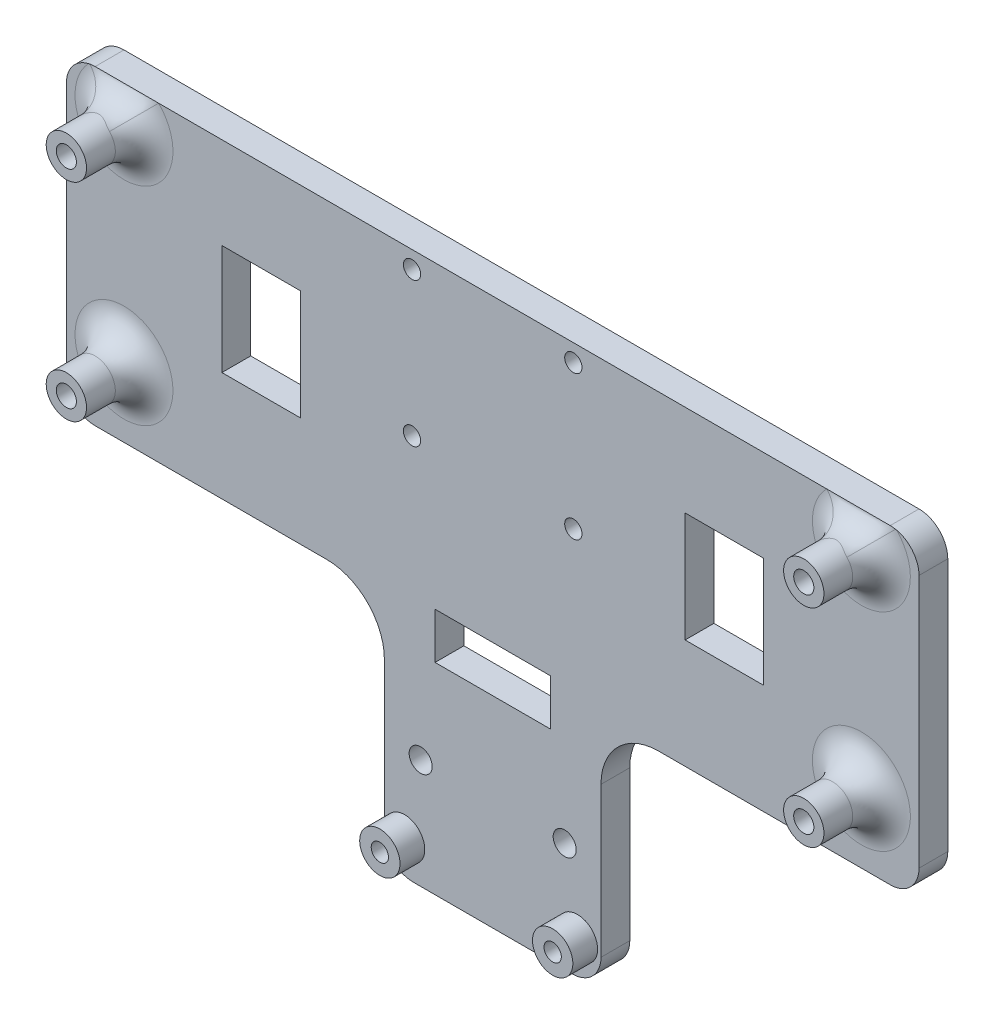
SolidWorks part; units mm, degrees
ref_plane "Front Plane" through (0, 0, 0) normal (0, 0, 1) x (1, 0, 0)
ref_plane "Top Plane" through (0, 0, 0) normal (0, 1, 0) x (1, 0, 0)
ref_plane "Right Plane" through (0, 0, 0) normal (1, 0, 0) x (0, 0, -1)
sketch "Sketch1" plane through (0, 0, 0) normal (0, 1, 0) x (1, 0, 0)
  line L0 (0, 0) -> (0, 178.218) construction
  line L1 (61, 138.218) -> (74, 138.218)
  line L2 (74, 138.218) -> (74, 181.218)
  line L3 (74, 181.218) -> (-74, 181.218)
  line L4 (0, 181.218) -> (0, 178.218)
  line L5 (-71, 178.218) -> (71, 178.218)
  line L6 (71, 178.218) -> (71, 143.218)
  line L7 (71, 143.218) -> (61, 143.218)
  line L8 (61, 143.218) -> (61, 138.218)
  line L9 (-61, 143.218) -> (-61, 138.218)
  line L10 (-71, 143.218) -> (-61, 143.218)
  line L11 (-71, 178.218) -> (-71, 143.218)
  line L12 (-74, 138.218) -> (-74, 181.218)
  line L13 (-61, 138.218) -> (-74, 138.218)
  dimension "D1" = 10
  dimension "D2" = 5
  dimension "D3" = 74
  dimension "D4" = 3
  dimension "D5" = 3
  dimension "D6" = 35
extrude "Boss-Extrude1" add sketch "Sketch1" along normal blind 110 contours L13 L9 L10 L11 L5 L4 L3 L12 | L7 L8 L1 L2 L3 L4 L5 L6
sketch "Sketch2" plane through (74, 0, 0) normal (1, 0, 0) x (0, 0, -1)
  line L0 (138.218, 66.5) -> (165.218, 66.5)
  line L1 (138.218, 110) -> (138.218, 0) construction
  line L2 (165.218, 66.5) -> (165.218, 100.5)
  line L3 (165.218, 100.5) -> (138.218, 100.5)
  line L4 (138.218, 100.5) -> (138.218, 66.5)
  line L5 (138.218, 110) -> (181.218, 110) construction
  dimension "D1" = 34
  dimension "D2" = 9.5
  dimension "D3" = 27
extrude "Cut-Extrude1" cut sketch "Sketch2" against normal blind 171
sketch "Sketch5" plane through (0, 0, -138.218) normal (0, 0, 1) x (1, 0, 0)
  line L0 (-61, 66.5) -> (-71, 66.5)
  line L1 (-74, 66.5) -> (-61, 66.5) construction
  line L2 (-71, 66.5) -> (-71, 54)
  line L3 (-71, 54) -> (-61, 54)
  line L4 (-61, 66.5) -> (-61, 0) construction
  line L5 (-61, 54) -> (-61, 66.5)
  line L6 (0, 0) -> (0, 110) construction
  line L7 (-71, 0) -> (71, 0) construction
  line L8 (-71, 110) -> (71, 110) construction
  line L9 (61, 54) -> (61, 66.5)
  line L10 (71, 54) -> (61, 54)
  line L11 (71, 66.5) -> (71, 54)
  line L12 (61, 66.5) -> (71, 66.5)
  dimension "D1" = 12.5
extrude "Cut-Extrude4" cut sketch "Sketch5" against normal blind 10 contours L5 L0 L2 L3 | L9 L12 L11 L10
sketch "Sketch7" plane through (74, 0, 0) normal (1, 0, 0) x (0, 0, -1)
  line L0 (181.218, 110) -> (138.218, 110)
  line L1 (138.218, 110) -> (138.218, 54)
  line L2 (138.218, 66.5) -> (138.218, 0) construction
  line L3 (138.218, 54) -> (181.218, 54)
  line L4 (181.218, 110) -> (181.218, 0) construction
  line L5 (181.218, 54) -> (181.218, 110)
  dimension "D1" = 56
extrude "Cut-Extrude5" cut sketch "Sketch7" against normal blind 280
sketch "Sketch9" plane through (0, 0, -181.218) normal (0, 0, -1) x (-1, 0, 0)
  line L0 (0, 0) -> (0, -92.5) construction
  line L1 (-75, -92.5) -> (75, -92.5) construction
  line L2 (18.8, 0) -> (18.8, -41)
  line L3 (-74, 0) -> (74, 0) construction
  line L4 (18.8, -41) -> (-18.8, -41)
  line L5 (0, -41) -> (0, 0)
  line L6 (-18.8, 0) -> (18.8, 0)
  line L7 (-18.8, 0) -> (-18.8, -41)
  circle A0 centre (15.285, -35.0992) radius 1.5
  circle A1 centre (-14.715, -35.0992) radius 1.5
  line M9 (-74, 0) -> (74, 0)
  dimension "D1" = 18.8
  dimension "D2" = 41
extrude "Boss-Extrude3" add sketch "Sketch9" against normal blind 3 contours L5 L4 L2 A0 M9 | L7 L4 L5 A1 M9
fillet "Fillet2" radius 10 4 edges at (71, 27, -178.218) (-71, 27, -178.218) (18.8, 0, -179.718) (-18.8, 0, -179.718)
sketch "Sketch11" plane through (0, 0, -181.218) normal (0, 0, -1) x (-1, 0, 0)
  line L0 (33.7, 19.3) -> (33.7, 37.8)
  line L1 (33.7, 37.8) -> (46.7, 37.8)
  line L2 (46.7, 37.8) -> (46.7, 19.3)
  line L3 (46.7, 19.3) -> (33.7, 19.3)
  circle A0 centre (-14, 51) radius 1.5
  circle A1 centre (-14, 26) radius 1.5
  circle A2 centre (14, 26) radius 1.5
  circle A3 centre (14, 51) radius 1.5
extrude "Cut-Extrude6" cut sketch "Sketch11" against normal blind 4.3
sketch "Sketch12" plane through (0, 0, -181.218) normal (0, 0, -1) x (-1, 0, 0)
  line L0 (18.8, -41) -> (-18.8, -41) construction
  line L26 (-6.8, -11.075) -> (-6.8, -30.175)
  line L27 (6.8, -30.175) -> (6.8, -11.075)
  line L28 (6.8, -11.075) -> (-6.8, -11.075)
  line L29 (-6.8, -30.175) -> (6.8, -30.175)
  dimension "D1" = 10.825
  dimension "D2" = 19.1
extrude "Cut-Extrude7" cut sketch "Sketch12" against normal blind 4.3
sketch "Sketch13" plane through (0, 0, -138.218) normal (0, 0, 1) x (1, 0, 0)
  circle A0 centre (64, 12) radius 2.25
  circle A1 centre (64, 48) radius 2.25
  circle A2 centre (-64, 12) radius 2.25
  circle A3 centre (-64, 48) radius 2.25
extrude "Cut-Extrude8" cut sketch "Sketch13" against normal blind 5
sketch "Sketch15" plane through (74, 0, 0) normal (1, 0, 0) x (0, 0, -1)
  line L0 (138.218, 54) -> (138.218, 45)
  line L1 (138.218, 54) -> (138.218, 0) construction
  line L2 (138.218, 45) -> (153.218, 45)
  line L3 (153.218, 45) -> (153.218, 30)
  line L4 (153.218, 30) -> (138.218, 30)
  line L5 (138.218, 30) -> (138.218, 45)
  line L6 (138.218, 54) -> (181.218, 54) construction
  line M5 (138.218, 54) -> (138.218, 0)
  dimension "D1" = 9
  dimension "D2" = 15
  dimension "D3" = 15
extrude "Cut-Extrude10" cut sketch "Sketch15" against normal blind 15.3 contours L4 L3 L2 M5
sketch "Sketch16" plane through (0, -41, 0) normal (0, -1, 0) x (-1, 0, 0)
  line L1 (-74, 178.218) -> (-74, 138.218)
  line L2 (-74, 138.218) -> (-61, 138.218)
  line L3 (-61, 138.218) -> (-61, 143.218)
  line L4 (-61, 143.218) -> (-71, 143.218)
  line L5 (-71, 143.218) -> (-18.8, 178.218)
  line L6 (0, 181.218) -> (0, 201.6639)
  line L7 (18.8, 181.218) -> (-18.8, 181.218) construction
  line L10 (71, 143.218) -> (18.8, 178.218)
  line L11 (61, 143.218) -> (71, 143.218)
  line L12 (61, 138.218) -> (61, 143.218)
  line L13 (74, 138.218) -> (61, 138.218)
  line L16 (-18.8, 178.218) -> (-74, 178.218)
  line L17 (18.8, 178.218) -> (74, 178.218)
  line L18 (74, 138.218) -> (74, 181.218) construction
  line L19 (74, 178.218) -> (74, 138.218)
extrude "Cut-Extrude11" cut sketch "Sketch16" against normal through all contours L19 L17 L10 L11 L12 L13 | L5 L16 L1 L2 L3 L4
sketch "Sketch17" plane through (0, 0, -178.218) normal (0, 0, 1) x (1, 0, 0)
  circle A0 centre (64, 12) radius 1.75
  circle A1 centre (64, 48) radius 1.75
  circle A2 centre (-64, 48) radius 1.75
  circle A3 centre (-64, 12) radius 1.75
  dimension "D1" = 3.5
  dimension "D2" = 3.5
  dimension "D3" = 3.5
  dimension "D4" = 3.5
extrude "Cut-Extrude12" cut sketch "Sketch17" against normal blind 10
sketch "Sketch18" plane through (0, 0, -178.218) normal (0, 0, 1) x (1, 0, 0)
  circle A0 centre (64, 12) radius 3.5
  circle A1 centre (64, 48) radius 3.5
  circle A2 centre (-64, 48) radius 3.5
  circle A3 centre (-64, 12) radius 3.5
  circle A4 centre (64, 48) radius 1.75
  circle A5 centre (64, 12) radius 1.75
  circle A6 centre (-64, 12) radius 1.75
  circle A7 centre (-64, 48) radius 1.75
  dimension "D1" = 7
  dimension "D2" = 7
  dimension "D3" = 7
  dimension "D4" = 7
extrude "Boss-Extrude5" add sketch "Sketch18" along normal blind 10
sketch "Sketch19" plane through (0, 0, -181.218) normal (0, 0, -1) x (-1, 0, 0)
  line L0 (0, -11.075) -> (0, 54) construction
  line L1 (6.8, -11.075) -> (-6.8, -11.075) construction
  line L2 (74, 54) -> (-74, 54) construction
  line L3 (10, -6.075) -> (-10, -6.075)
  line L4 (-10, -6.075) -> (-10, 1.925)
  line L5 (-10, 1.925) -> (10, 1.925)
  line L6 (10, 1.925) -> (10, -6.075)
  dimension "D1" = 20
  dimension "D2" = 10
  dimension "D3" = 8
  dimension "D4" = 5
extrude "Cut-Extrude13" cut sketch "Sketch19" against normal blind 10
sketch "Sketch20" plane through (0, 0, -181.218) normal (0, 0, -1) x (-1, 0, 0)
  line L0 (6.8, -30.175) -> (-6.8, -30.175)
  line L1 (-6.8, -30.175) -> (-6.8, -11.075)
  line L2 (-6.8, -11.075) -> (6.8, -11.075)
  line L3 (6.8, -11.075) -> (-6.8, -11.075) construction
  line L4 (6.8, -11.075) -> (6.8, -30.175)
  line L5 (-33.4, 19) -> (-47, 19)
  line L6 (-47, 19) -> (-47, 38.1)
  line L7 (-47, 38.1) -> (-33.4, 38.1)
  line L8 (-33.4, 38.1) -> (-33.4, 19)
  line L9 (-74, 54) -> (-74, 0) construction
  line L10 (-74, 0) -> (-28.8, 0) construction
  dimension "D1" = 13.6
  dimension "D2" = 19.1
  dimension "D3" = 19.1
  dimension "D4" = 13.6
  dimension "D5" = 27
  dimension "D6" = 19
extrude "Cut-Extrude14" cut sketch "Sketch20" against normal blind 10
sketch "Sketch21" plane through (0, 0, -181.218) normal (0, 0, -1) x (-1, 0, 0)
  line L0 (74, 0) -> (74, 54)
  line L1 (74, 54) -> (-74, 54)
  line L2 (-74, 54) -> (-74, 0)
  line L3 (-74, 0) -> (-28.8, 0)
  line L4 (-18.8, -10) -> (-18.8, -41)
  line L5 (-18.8, -41) -> (18.8, -41)
  line L6 (18.8, -41) -> (18.8, -10)
  line L7 (28.8, 0) -> (74, 0)
  line L8 (6.8, -30.175) -> (6.8, -11.075)
  line L9 (6.8, -11.075) -> (-6.8, -11.075)
  line L10 (-6.8, -11.075) -> (-6.8, -30.175)
  line L11 (-6.8, -30.175) -> (6.8, -30.175)
  line L12 (-10, 1.925) -> (-10, -6.075)
  line L13 (-10, -6.075) -> (10, -6.075)
  line L14 (10, -6.075) -> (10, 1.925)
  line L15 (10, 1.925) -> (-10, 1.925)
  line L16 (-33.4, 19) -> (-33.4, 38.1)
  line L17 (-33.4, 38.1) -> (-47, 38.1)
  line L18 (-47, 38.1) -> (-47, 19)
  line L19 (-47, 19) -> (-33.4, 19)
  arc A0 (-28.8, 0) -> (-18.8, -10) centre (-28.8, -10) cw
  arc A1 (18.8, -10) -> (28.8, 0) centre (28.8, -10) cw
  arc A2 (28.8, 0) -> (18.8, -10) centre (28.8, -10) ccw construction
  circle A3 centre (15.285, -35.0992) radius 1.5
  circle A4 centre (-14.715, -35.0992) radius 1.5
  circle A5 centre (-14, 26) radius 1.5
  circle A6 centre (-14, 51) radius 1.5
  circle A7 centre (-64, 12) radius 1.75
  circle A8 centre (-64, 48) radius 1.75
  circle A9 centre (14, 51) radius 1.5
  circle A10 centre (14, 26) radius 1.5
  circle A11 centre (64, 12) radius 1.75
  circle A12 centre (64, 48) radius 1.75
  circle A13 centre (12.5, -22) radius 2
  circle A14 centre (-12.5, -22) radius 2
extrude "Boss-Extrude6" add sketch "Sketch21" along normal blind 2
fillet "Fillet3" radius 5 4 edges at (-67.5, 12, -178.218) (-67.5, 48, -178.218) (60.5, 48, -178.218) (60.5, 12, -178.218)
fillet "Fillet4" radius 5 6 edges at (-74, 54, -180.718) (-18.8, -41, -180.718) (18.8, -41, -180.718) (74, 54, -180.718) (74, 0, -180.718) (-74, 0, -180.718)
sketch "Sketch10" plane through (0, 0, -178.218) normal (0, 0, 1) x (1, 0, 0)
  circle A0 centre (14.715, -35.0992) radius 3.5
  circle A1 centre (-15.285, -35.0992) radius 3.5
  circle A2 centre (14.715, -35.0992) radius 1.5
  circle A3 centre (-15.285, -35.0992) radius 1.5
  dimension "D1" = 7
  dimension "D2" = 7
extrude "Boss-Extrude4" add sketch "Sketch10" along normal blind 4.3
sketch "Sketch22" plane through (0, 0, -183.218) normal (0, 0, -1) x (-1, 0, 0)
  line L0 (6.8, -30.175) -> (6.8, -11.075)
  line L1 (6.8, -11.075) -> (-6.8, -11.075)
  line L2 (-6.8, -11.075) -> (-6.8, -30.175)
  line L3 (-6.8, -30.175) -> (6.8, -30.175)
extrude "Boss-Extrude7" add sketch "Sketch22" against normal blind 5
sketch "Sketch23" plane through (0, 0, -183.218) normal (0, 0, -1) x (-1, 0, 0)
  line L0 (0, -41) -> (0, 54) construction
  line L1 (-13.8, -41) -> (13.8, -41) construction
  line L2 (69, 54) -> (-69, 54) construction
  line L3 (-33.4, 19) -> (-47, 19)
  line L4 (-47, 19) -> (-47, 38.1)
  line L5 (-47, 38.1) -> (-33.4, 38.1)
  line L6 (-33.4, 38.1) -> (-33.4, 19)
  line L7 (33.4, 38.1) -> (33.4, 19)
  line L8 (47, 38.1) -> (33.4, 38.1)
  line L9 (47, 19) -> (47, 38.1)
  line L10 (33.4, 19) -> (47, 19)
extrude "Cut-Extrude15" cut sketch "Sketch23" against normal blind 5
sketch "Sketch25" plane through (0, 0, -183.218) normal (0, 0, -1) x (-1, 0, 0)
  circle A0 centre (12.5, -22) radius 2
  circle A1 centre (-12.5, -22) radius 2
extrude "Cut-Extrude16" cut sketch "Sketch25" against normal blind 7
